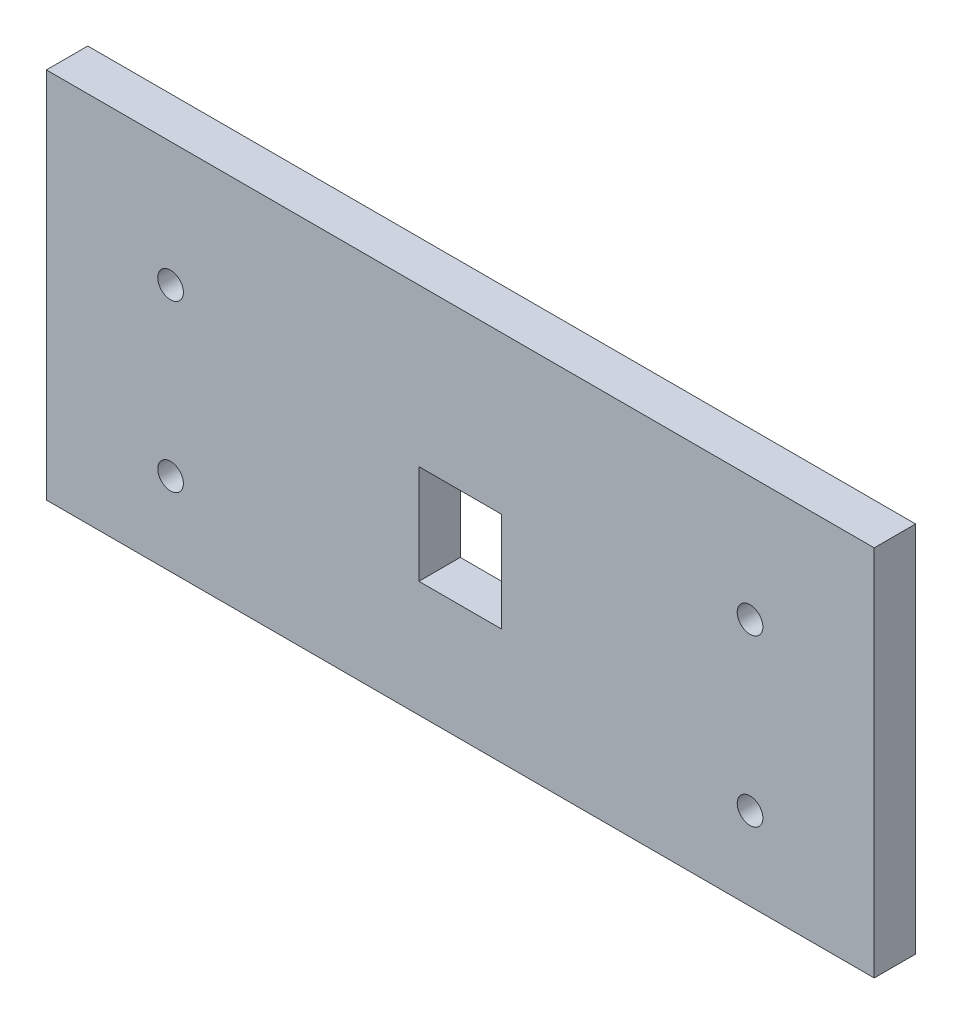
SolidWorks part; units mm, degrees
ref_plane "Plan de face" through (0, 0, 0) normal (0, 0, 1) x (1, 0, 0)
ref_plane "Plan de dessus" through (0, 0, 0) normal (0, 1, 0) x (1, 0, 0)
ref_plane "Plan de droite" through (0, 0, 0) normal (1, 0, 0) x (0, 0, -1)
sketch "Esquisse1" plane through (0, 0, 0) normal (0, 0, 1) x (1, 0, 0)
  line L0 (0, 0) -> (28.085, 0) construction
  line L1 (-50, -22.5) -> (50, -22.5)
  line L2 (-50, -22.5) -> (-50, 22.5)
  line L3 (-50, 22.5) -> (50, 22.5)
  line L4 (50, -22.5) -> (50, 22.5)
  line L5 (-50, -22.5) -> (50, 22.5) construction
  line L6 (-50, 22.5) -> (50, -22.5) construction
  line L7 (0, 0) -> (0, 16.2531) construction
  line L8 (0, 0) -> (0, -2.5) construction
  line L13 (-5, -8.5) -> (5, -8.5)
  line L14 (-5, -8.5) -> (-5, 3.5)
  line L15 (-5, 3.5) -> (5, 3.5)
  line L16 (5, -8.5) -> (5, 3.5)
  line L17 (-5, -8.5) -> (5, 3.5) construction
  line L18 (-5, 3.5) -> (5, -8.5) construction
  circle A0 centre (-35, -12.5) radius 1.55
  circle A1 centre (35, -12.5) radius 1.55
  circle A4 centre (35, 7.5) radius 1.55
  circle A5 centre (-35, 7.5) radius 1.55
  point P0 (0, 0)
  point P17 (0.8333, -1.5)
  dimension "D3" = 3.1
  dimension "D5" = 15
  dimension "D9" = 3.1
  dimension "D1" = 100
  dimension "D2" = 45
  dimension "D4" = 20
  dimension "D6" = 10
  dimension "D7" = 12
  dimension "D8" = 10
  dimension "D10" = 15
  dimension "D11" = 15
extrude "Boss.-Extru.1" add sketch "Esquisse1" against normal blind 5
